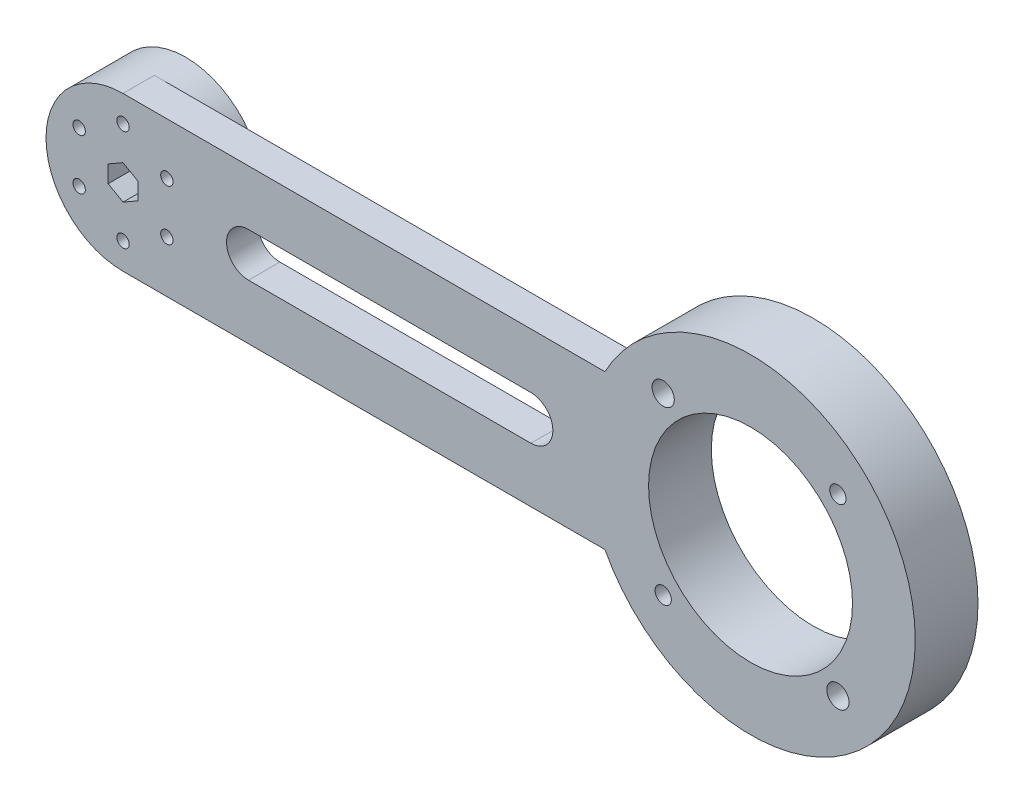
SolidWorks part; units mm, degrees
material "Cast Stainless Steel"
ref_plane "Front Plane" through (0, 0, 0) normal (0, 0, 1) x (1, 0, 0)
ref_plane "Top Plane" through (0, 0, 0) normal (0, 1, 0) x (1, 0, 0)
ref_plane "Right Plane" through (0, 0, 0) normal (1, 0, 0) x (0, 0, -1)
sketch "Sketch1" plane through (0, 0, 0) normal (0, 0, 1) x (1, 0, 0)
  line L0 (-76.3667, 3.0779) -> (-73.3667, 1.3459)
  line L1 (-73.3667, 1.3459) -> (-73.3667, -2.1182)
  line L2 (-73.3667, -2.1182) -> (-76.3667, -3.8503)
  line L3 (-76.3667, -3.8503) -> (-79.3667, -2.1182)
  line L4 (-79.3667, -2.1182) -> (-79.3667, 1.3459)
  line L5 (-79.3667, 1.3459) -> (-76.3667, 3.0779)
  line L6 (-76.3667, 15.1986) -> (21.1629, 15.1986)
  line L7 (-76.3667, -15.9709) -> (21.1629, -15.9709)
  line L8 (-50.9667, -0.3862) -> (6.1833, -0.3862) construction
  line L9 (-50.9667, 4.0588) -> (6.1833, 4.0588)
  line L10 (-50.9667, -4.8312) -> (6.1833, -4.8312)
  circle A0 centre (32.9557, 17.2915) radius 2.25
  circle A1 centre (68.311, 17.2915) radius 1.65
  circle A2 centre (68.311, -18.0638) radius 2.25
  circle A3 centre (32.9557, -18.0638) radius 1.65
  circle A4 centre (50.6333, -0.3862) radius 20.6375
  circle A5 centre (50.6333, -0.3862) radius 33.3375
  circle A6 centre (-76.3667, -0.3862) radius 15.5847
  circle A7 centre (-76.3667, 9.8638) radius 1.25
  circle A8 centre (-85.2434, 4.7388) radius 1.25
  circle A9 centre (-85.2434, -5.5112) radius 1.25
  circle A10 centre (-76.3667, -10.6362) radius 1.25
  circle A11 centre (-67.4899, -5.5112) radius 1.25
  circle A12 centre (-67.4899, 4.7388) radius 1.25
  arc A13 (-76.3667, 15.1986) -> (-76.3667, -15.9709) centre (-76.3667, -0.3862) cw
  arc A14 (21.1629, 15.1986) -> (21.1629, -15.9709) centre (50.6333, -0.3862) ccw
  arc A15 (-50.9667, 4.0588) -> (-50.9667, -4.8312) centre (-50.9667, -0.3862) ccw
  arc A16 (6.1833, -4.8312) -> (6.1833, 4.0588) centre (6.1833, -0.3862) ccw
  point P19 (-22.3917, -0.3862)
  dimension "D1" = 2.5
  dimension "D2" = 31.1694
  dimension "D3" = 41.275
  dimension "D4" = 66.675
  dimension "D5" = 4.5
  dimension "D6" = 3.3
  dimension "D7" = 4.445
  dimension "D8" = 6.1833
  dimension "D9" = 21.1629
  dimension "D10" = 32.9557
  dimension "D11" = 68.311
  dimension "D12" = 22.3917
  dimension "D13" = 67.4899
  dimension "D14" = 73.3667
  dimension "D15" = 76.3667
  dimension "D16" = 85.2434
  dimension "D17" = 3.0779
  dimension "D18" = 17.2915
  dimension "D19" = 4.7388
  dimension "D20" = 9.8638
  dimension "D21" = 0.3862
  dimension "D22" = 2.1182
  dimension "D25" = 5.5112
  dimension "D26" = 10.6362
  dimension "D27" = 18.0638
extrude "Boss-Extrude1" add sketch "Sketch1" along normal blind 6.35 contours A6 A12 A11 A10 A9 A8 A7 L4 L5 L0 L1 L2 L3 | A6 L7 A5 L6 A16 L10 A15 L9 | A5 A0 A1 A2 A3 A4 region at (-27.6019, 14.1747, 0) region at (-65.6583, 10.3222, 0) region at (58.4349, 31.055, 0)
extrude "Boss-Extrude2" add sketch "Sketch1<3>" against normal blind 6.35 contours A5 A0 A1 A2 A3 A4 | A6 A12 A11 A10 A9 A8 A7 L4 L5 L0 L1 L2 L3 region at (-65.6583, 10.3222, 0) region at (58.4349, 31.055, 0)
sketch "Sketch1<3>" plane through (0, 0, 0) normal (0, 0, 1) x (1, 0, 0) same geometry as "Sketch1"
